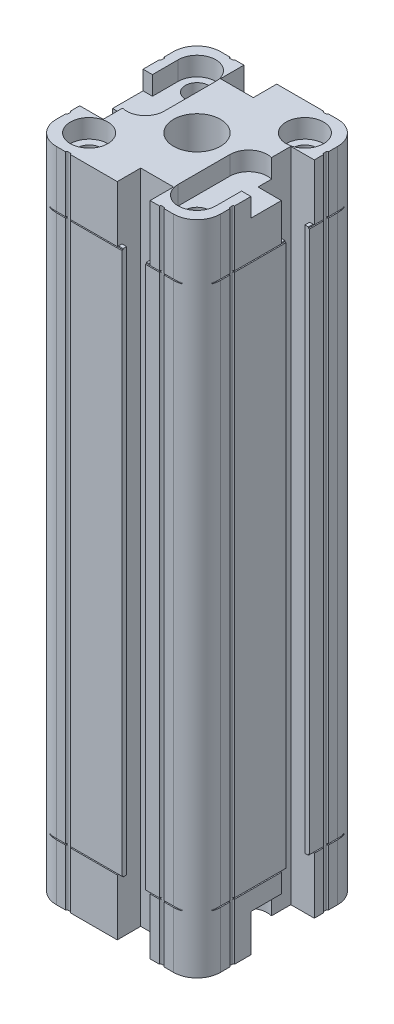
SolidWorks part; units mm, degrees
ref_plane "Front Plane" through (0, 0, 0) normal (0, 0, 1) x (1, 0, 0)
ref_plane "Top Plane" through (0, 0, 0) normal (0, 1, 0) x (1, 0, 0)
ref_plane "Right Plane" through (0, 0, 0) normal (1, 0, 0) x (0, 0, -1)
sketch "Sketch1" plane through (0, 0, 0) normal (0, 1, 0) x (1, 0, 0)
  line L1 (0, 0) -> (35, 0)
  line L2 (0, 0) -> (0, 35)
  line L3 (0, 35) -> (35, 35)
  line L4 (35, 0) -> (35, 35)
  dimension "D1" = 35
  dimension "D2" = 35
extrude "Boss-Extrude1" add sketch "Sketch1" along normal blind 140
sketch "Sketch2" plane through (0, 0, 0) normal (0, -1, 0) x (-1, 0, 0)
  line L0 (0, 0) -> (-35, 0) construction
  line L1 (0, 35) -> (0, 0) construction
  line L2 (-29, 6) -> (-29, 17) construction
  line L3 (-33, 6) -> (-33, 17)
  line L4 (-25, 6) -> (-25, 17)
  line L5 (-35, 0) -> (-35, 35) construction
  line L6 (-35, 35) -> (0, 35) construction
  line L7 (-6, 18) -> (-6, 29) construction
  line L8 (-10, 18) -> (-10, 29)
  line L9 (-2, 18) -> (-2, 29)
  circle A0 centre (-6, 6) radius 4
  circle A1 centre (-29, 29) radius 4
  arc A2 (-33, 6) -> (-25, 6) centre (-29, 6) ccw
  arc A3 (-25, 17) -> (-33, 17) centre (-29, 17) ccw
  arc A4 (-10, 18) -> (-2, 18) centre (-6, 18) ccw
  arc A5 (-2, 29) -> (-10, 29) centre (-6, 29) ccw
  point P10 (-29, 11.5)
  point P21 (-6, 23.5)
  dimension "D1" = 8
  dimension "D4" = 4
  dimension "D5" = 11
  dimension "D10" = 4
  dimension "D11" = 6
  dimension "D2" = 6
  dimension "D3" = 6
  dimension "D6" = 6
  dimension "D7" = 6
  dimension "D8" = 6
  dimension "D9" = 11
extrude "Cut-Extrude1" cut sketch "Sketch2" against normal blind 8
sketch "Sketch3" plane through (0, 0, 0) normal (0, -1, 0) x (-1, 0, 0)
  line L0 (0, 35) -> (0, 0) construction
  line L1 (-5, 23.5) -> (0, 23.5)
  line L2 (-5, 23.5) -> (-5, 14.127)
  line L3 (-5, 14.127) -> (0, 14.127)
  line L4 (0, 23.5) -> (0, 14.127)
  line L5 (-2, 18) -> (-2, 29) construction
  line L6 (-35, 20.873) -> (-30, 20.873)
  line L7 (-35, 20.873) -> (-35, 11.5)
  line L8 (-35, 11.5) -> (-30, 11.5)
  line L9 (-30, 20.873) -> (-30, 11.5)
  line L10 (-35, 0) -> (-35, 35) construction
  line L11 (-33, 17) -> (-33, 6) construction
  arc A2 (-25, 17) -> (-33, 17) centre (-29, 17) ccw construction
  arc A3 (-10, 18) -> (-2, 18) centre (-6, 18) ccw construction
  point P13 (-2, 23.5)
  point P25 (-32.5, 20.873)
  point P34 (-33, 11.5)
  dimension "D1" = 5
  dimension "D2" = 5
extrude "Cut-Extrude2" cut sketch "Sketch3" against normal up to surface (8 mm away) up to face at (6, 8, -23.5)
sketch "Sketch5" plane through (0, 0, 0) normal (0, -1, 0) x (1, 0, 0)
  line L0 (35, -20.873) -> (35, -35) construction
  line L1 (5, -17) -> (0, -17)
  line L2 (5, -17) -> (5, -10)
  line L3 (5, -10) -> (0, -10)
  line L4 (0, -17) -> (0, -10)
  line L5 (30, -18) -> (35, -18)
  line L6 (30, -18) -> (30, -25)
  line L7 (30, -25) -> (35, -25)
  line L8 (35, -18) -> (35, -25)
  line L9 (0, 0) -> (35, 0) construction
  line L10 (18, 0) -> (25, 0)
  line L11 (18, 0) -> (18, -5)
  line L12 (18, -5) -> (25, -5)
  line L13 (25, 0) -> (25, -5)
  line L14 (35, -35) -> (0, -35) construction
  line L15 (10, -35) -> (17, -35)
  line L16 (10, -35) -> (10, -30)
  line L17 (10, -30) -> (17, -30)
  line L18 (17, -35) -> (17, -30)
  circle A0 centre (6, -6) radius 4 construction
  circle A1 centre (29, -29) radius 4 construction
  dimension "D1" = 7
  dimension "D2" = 7
  dimension "D3" = 5
  dimension "D4" = 7
  dimension "D5" = 10
  dimension "D6" = 7
  dimension "D7" = 5
  dimension "D8" = 10
extrude "Cut-Extrude3" cut sketch "Sketch5" against normal blind 12
sketch "Sketch6" plane through (0, 12, 0) normal (0, -1, 0) x (1, 0, 0)
  line L6 (0, -16) -> (1, -16)
  line L7 (0, -10) -> (0, -17) construction
  line L8 (1, -16) -> (1, -17)
  line L9 (0, -17) -> (5, -17) construction
  line L10 (1, -17) -> (5, -17)
  line L11 (5, -17) -> (5, -10)
  line L12 (5, -10) -> (1, -10)
  line L13 (5, -10) -> (0, -10) construction
  line L14 (1, -10) -> (1, -11)
  line L15 (1, -11) -> (0, -11)
  line L16 (0, -11) -> (0, -16)
  line L17 (19, 0) -> (19, -1)
  line L18 (25, 0) -> (18, 0) construction
  line L19 (19, -1) -> (18, -1)
  line L20 (18, 0) -> (18, -5) construction
  line L21 (18, -1) -> (18, -5)
  line L22 (18, -5) -> (25, -5)
  line L23 (25, -5) -> (25, -1.01)
  line L24 (25, -5) -> (25, 0) construction
  line L25 (25, -1.01) -> (24, -1.01)
  line L26 (24, -1.01) -> (24, 0)
  line L27 (24, 0) -> (19, 0)
  line L28 (35, -19) -> (34, -19)
  line L29 (35, -25) -> (35, -18) construction
  line L30 (34, -19) -> (34, -18)
  line L31 (35, -18) -> (30, -18) construction
  line L32 (34, -18) -> (30, -18)
  line L33 (30, -18) -> (30, -25)
  line L34 (30, -25) -> (34, -25)
  line L35 (30, -25) -> (35, -25) construction
  line L36 (34, -25) -> (34, -24)
  line L37 (34, -24) -> (35, -24)
  line L38 (35, -24) -> (35, -19)
  line L39 (11, -35) -> (11, -34)
  line L40 (10, -35) -> (17, -35) construction
  line L41 (11, -34) -> (10, -34)
  line L42 (10, -30) -> (10, -35) construction
  line L43 (10, -34) -> (10, -30)
  line L44 (10, -30) -> (17, -30)
  line L45 (17, -30) -> (17, -34)
  line L46 (17, -35) -> (17, -30) construction
  line L47 (17, -34) -> (16, -34)
  line L48 (16, -34) -> (16, -35)
  line L49 (16, -35) -> (11, -35)
  dimension "D1" = 1
  dimension "D2" = 1
  dimension "D3" = 1
  dimension "D4" = 1
extrude "Cut-Extrude4" cut sketch "Sketch6" against normal blind 116
sketch "Sketch7" plane through (0, 140, 0) normal (0, 1, 0) x (1, 0, 0)
  line L0 (6, 29) -> (6, 18) construction
  line L1 (10, 29) -> (10, 18)
  line L2 (2, 29) -> (2, 18)
  line L3 (29, 17) -> (29, 6) construction
  line L4 (33, 17) -> (33, 6)
  line L5 (25, 17) -> (25, 6)
  arc A2 (10, 29) -> (2, 29) centre (6, 29) ccw
  arc A6 (2, 18) -> (10, 18) centre (6, 18) ccw
  circle A8 centre (29, 29) radius 4
  arc A9 (10, 29) -> (2, 29) centre (6, 29) ccw construction
  arc A10 (33, 17) -> (25, 17) centre (29, 17) ccw
  arc A11 (25, 6) -> (33, 6) centre (29, 6) ccw
  arc A12 (33, 17) -> (25, 17) centre (29, 17) ccw construction
  circle A13 centre (6, 6) radius 4
  point P4 (6, 23.5)
  point P14 (29, 11.5)
extrude "Cut-Extrude5" cut sketch "Sketch7" against normal blind 4
sketch "Sketch9" plane through (0, 140, 0) normal (0, 1, 0) x (1, 0, 0)
  line L1 (0, 23.5) -> (5, 23.5)
  line L2 (0, 23.5) -> (0, 14.127)
  line L3 (0, 14.127) -> (5, 14.127)
  line L4 (5, 23.5) -> (5, 14.127)
  line L5 (35, 20.873) -> (30, 20.873)
  line L6 (35, 20.873) -> (35, 11.5)
  line L7 (35, 11.5) -> (30, 11.5)
  line L8 (30, 20.873) -> (30, 11.5)
extrude "Cut-Extrude7" cut sketch "Sketch9" against normal up to surface (4 mm away) up to face at (6, 136, -23.5)
sketch "Sketch10" plane through (0, 140, 0) normal (0, 1, 0) x (1, 0, 0)
  line L1 (10, 30) -> (17, 30)
  line L2 (10, 30) -> (10, 35)
  line L3 (10, 35) -> (17, 35)
  line L4 (17, 30) -> (17, 35)
  line L5 (35, 25) -> (30, 25)
  line L6 (35, 25) -> (35, 18)
  line L7 (35, 18) -> (30, 18)
  line L8 (30, 25) -> (30, 18)
  line L9 (5, 10) -> (0, 10)
  line L10 (5, 10) -> (5, 17)
  line L11 (5, 17) -> (0, 17)
  line L12 (0, 10) -> (0, 17)
  line L13 (25, 5) -> (18, 5)
  line L14 (25, 5) -> (25, 0)
  line L15 (25, 0) -> (18, 0)
  line L16 (18, 5) -> (18, 0)
extrude "Cut-Extrude8" cut sketch "Sketch10" against normal blind 12
sketch "Sketch11" plane through (0, 140, 0) normal (0, 1, 0) x (1, 0, 0)
  line L0 (10, 35) -> (0, 35) construction
  line L1 (7, 35) -> (8, 35)
  line L2 (7, 35) -> (7, 34.75)
  line L3 (7, 34.75) -> (8, 34.75)
  line L4 (8, 35) -> (8, 34.75)
  line L5 (0, 35) -> (0, 23.5) construction
  line L6 (35, 35) -> (17, 35) construction
  line L7 (27, 35) -> (28, 35)
  line L8 (27, 35) -> (27, 34.75)
  line L9 (27, 34.75) -> (28, 34.75)
  line L10 (28, 35) -> (28, 34.75)
  line L11 (35, 25) -> (35, 35) construction
  line L12 (35, 0) -> (35, 11.5) construction
  line L13 (35, 28) -> (34.75, 28)
  line L14 (35, 28) -> (35, 27)
  line L15 (35, 27) -> (34.75, 27)
  line L16 (34.75, 28) -> (34.75, 27)
  line L17 (35, 8) -> (34.75, 8)
  line L18 (35, 8) -> (35, 7)
  line L19 (35, 7) -> (34.75, 7)
  line L20 (34.75, 8) -> (34.75, 7)
  line L21 (25, 0) -> (35, 0) construction
  line L22 (27, 0) -> (28, 0)
  line L23 (27, 0) -> (27, 0.25)
  line L24 (27, 0.25) -> (28, 0.25)
  line L25 (28, 0) -> (28, 0.25)
  line L26 (0, 0) -> (18, 0) construction
  line L27 (8, 0) -> (7, 0)
  line L28 (8, 0) -> (8, 0.25)
  line L29 (8, 0.25) -> (7, 0.25)
  line L30 (7, 0) -> (7, 0.25)
  line L31 (0, 10) -> (0, 0) construction
  line L32 (0, 8) -> (0.25, 8)
  line L33 (0, 8) -> (0, 7)
  line L34 (0, 7) -> (0.25, 7)
  line L35 (0.25, 8) -> (0.25, 7)
  line L36 (10, 35) -> (0, 35) construction
  line L37 (0, 28) -> (0.25, 28)
  line L38 (0, 28) -> (0, 27)
  line L39 (0, 27) -> (0.25, 27)
  line L40 (0.25, 28) -> (0.25, 27)
  dimension "D1" = 7
  dimension "D2" = 1
  dimension "D3" = 0.25
  dimension "D4" = 7
  dimension "D5" = 7
  dimension "D6" = 7
  dimension "D7" = 7
  dimension "D8" = 7
  dimension "D9" = 7
  dimension "D10" = 7
extrude "Cut-Extrude9" cut sketch "Sketch11" against normal through all
fillet "Fillet2" radius 0.25 16 edges at (0.25, 70, -7) (0.25, 70, -8) (7, 70, -0.25) (8, 70, -0.25) (28, 70, -0.25) (27, 70, -0.25) (34.75, 70, -8) (34.75, 70, -7) (34.75, 70, -27) (34.75, 70, -28) (27, 70, -34.75) (28, 70, -34.75) (7, 70, -34.75) (8, 70, -34.75) (0.25, 70, -27) (0.25, 70, -28)
sketch "Sketch12" plane through (0, 0, 0) normal (-1, 0, 0) x (0, 0, 1)
  line L0 (-35, 140) -> (-35, 0) construction
  line L1 (-35, 12.25) -> (-34.75, 12.25)
  line L2 (-35, 12.25) -> (-35, 12)
  line L3 (-35, 12) -> (-34.75, 12)
  line L4 (-34.75, 12.25) -> (-34.75, 12)
  line L5 (0, 140) -> (0, 0) construction
  line L6 (0, 12.25) -> (-0.25, 12.25)
  line L7 (0, 12.25) -> (0, 12)
  line L8 (0, 12) -> (-0.25, 12)
  line L9 (-0.25, 12.25) -> (-0.25, 12)
  line L10 (-35, 0) -> (-28, 0) construction
  line L11 (-7, 0) -> (0, 0) construction
  line L12 (-35, 140) -> (-28, 140) construction
  line L13 (-35, 128) -> (-34.75, 128)
  line L14 (-35, 128) -> (-35, 127.75)
  line L15 (-35, 127.75) -> (-34.75, 127.75)
  line L16 (-34.75, 128) -> (-34.75, 127.75)
  line L17 (0, 128) -> (-0.25, 128)
  line L18 (0, 128) -> (0, 127.75)
  line L19 (0, 127.75) -> (-0.25, 127.75)
  line L20 (-0.25, 128) -> (-0.25, 127.75)
  line L21 (-7, 140) -> (0, 140) construction
  dimension "D1" = 0.25
  dimension "D2" = 0.25
  dimension "D3" = 0.25
  dimension "D4" = 0.25
  dimension "D5" = 12
  dimension "D6" = 12
  dimension "D7" = 0.25
  dimension "D8" = 0.25
  dimension "D9" = 0.25
  dimension "D10" = 0.25
  dimension "D11" = 12
  dimension "D12" = 12
fillet "Fillet4" radius 5 4 edges at (35, 70, 0) (0, 70, 0) (35, 70, -35) (0, 70, -35)
extrude "Cut-Extrude12" cut sketch "Sketch12" against normal through all
sketch "Sketch14" plane through (0, 0, 0) normal (0, 0, 1) x (1, 0, 0)
  line L0 (35, 140) -> (35, 0) construction
  line L1 (0, 128) -> (0.25, 128)
  line L2 (0, 128) -> (0, 127.75)
  line L3 (0, 127.75) -> (0.25, 127.75)
  line L4 (0.25, 128) -> (0.25, 127.75)
  line L9 (0, 12.25) -> (0, 12) construction
  line L10 (0, 12.25) -> (0.25, 12.25)
  line L11 (0, 12.25) -> (0, 12)
  line L12 (0, 12) -> (0.25, 12)
  line L13 (0.25, 12.25) -> (0.25, 12)
  line L14 (0, 12.25) -> (0, 12) construction
  line L16 (35, 12.25) -> (34.75, 12.25)
  line L17 (35, 12.25) -> (35, 12)
  line L18 (35, 12) -> (34.75, 12)
  line L19 (34.75, 12.25) -> (34.75, 12)
  line L20 (35, 128) -> (34.75, 128)
  line L21 (35, 128) -> (35, 127.75)
  line L22 (35, 127.75) -> (34.75, 127.75)
  line L23 (34.75, 128) -> (34.75, 127.75)
  dimension "D1" = 0.25
  dimension "D2" = 0.25
  dimension "D3" = 0.25
  dimension "D5" = 0.25
  dimension "D6" = 0.25
  dimension "D7" = 0.25
  dimension "D8" = 0.25
extrude "Cut-Extrude13" cut sketch "Sketch14" against normal through all
sketch "Sketch15" plane through (0, 8, 0) normal (0, -1, 0) x (-1, 0, 0)
  circle A0 centre (-6, 6) radius 2.5
  circle A1 centre (-29, 29) radius 2.5
  circle A3 centre (-29, 6) radius 2.5
  circle A4 centre (-6, 29) radius 2.5
  dimension "D1" = 5
extrude "Cut-Extrude14" cut sketch "Sketch15" against normal up to vertex (4 mm away) up to point (0.25, 12, -3.4388)
thread "Thread2" pitch 0.8 method extrude profile "Thread Profile2" start angle 0, offset 0, length 0, pitch 0.8, diameter 5
ref_plane "Plane2" through (31.5, 8, -6) normal (0, 0, 1) x (1, 0, 0)
sketch "Thread Profile2" plane through (31.5, 8, -6) normal (0, 0, 1) x (1, 0, 0)
  line L0 (0, 0) -> (0, 0.8) construction
  line L11 (0, 0) -> (0, 0.7)
  line L12 (0, 0.7) -> (-0.433, 0.45)
  line L13 (-0.433, 0.45) -> (-0.433, 0.25)
  line L15 (-0.433, 0.25) -> (0, 0)
  line L17 (-0.433, 0.35) -> (0, 0.35) construction
  point P2 (0, 0)
  dimension "Pitch" = 0.8
  dimension "Profile_Angle" = 60
  dimension "Profile_Land" = 0.2
  dimension "Profile_Height" = 0.433
thread "Thread3" pitch 0.8 method extrude profile "Thread Profile3" start angle 0, offset 0, length 0, pitch 0.8, diameter 5
ref_plane "Plane3" through (8.5, 8, -29) normal (0, 0, 1) x (1, 0, 0)
sketch "Thread Profile3" plane through (8.5, 8, -29) normal (0, 0, 1) x (1, 0, 0)
  line L0 (0, 0) -> (0, 0.8) construction
  line L11 (0, 0) -> (0, 0.7)
  line L12 (0, 0.7) -> (-0.433, 0.45)
  line L13 (-0.433, 0.45) -> (-0.433, 0.25)
  line L15 (-0.433, 0.25) -> (0, 0)
  line L17 (-0.433, 0.35) -> (0, 0.35) construction
  point P2 (0, 0)
  dimension "Pitch" = 0.8
  dimension "Profile_Angle" = 60
  dimension "Profile_Land" = 0.2
  dimension "Profile_Height" = 0.433
sketch "Sketch24" plane through (0, 136, 0) normal (0, 1, 0) x (1, 0, 0)
  circle A0 centre (6, 29) radius 2.5
  circle A1 centre (29, 29) radius 2.5
  circle A2 centre (6, 6) radius 2.5
  circle A3 centre (29, 6) radius 2.5
  dimension "D1" = 5
extrude "Cut-Extrude15" cut sketch "Sketch24" against normal up to vertex (8 mm away) up to point (35, 128, -5)
sketch "Sketch33" plane through (0, 0, 0) normal (0, -1, 0) x (-1, 0, 0)
  circle A0 centre (-18, 18) radius 6
  dimension "D1" = 12
extrude "Cut-Extrude16" cut sketch "Sketch33" against normal blind 3
sketch "Sketch35" plane through (0, 140, 0) normal (0, 1, 0) x (1, 0, 0)
  line L0 (27, 35) -> (17, 35) construction
  line L1 (0, 17) -> (0, 23.5) construction
  circle A0 centre (17.5, 17.5) radius 5
  dimension "D1" = 10
  dimension "D2" = 17.5
  dimension "D3" = 17.5
extrude "Cut-Extrude19" cut sketch "Sketch15<3>" against normal through all contours A1 | A0
sketch "Sketch15<3>" plane through (0, 8, 0) normal (0, -1, 0) x (-1, 0, 0) same geometry as "Sketch15"
ref_plane "Plane4" through (0, 127.75, 0) normal (0, 1, 0) x (1, 0, 0)
sketch "Sketch36" plane through (0, 127.75, 0) normal (0, 1, 0) x (1, 0, 0)
  line L0 (0, 27) -> (0, 23.5) construction
  line L1 (8.5, 26.5) -> (26.5, 26.5)
  line L2 (8.5, 26.5) -> (8.5, 8.5)
  line L3 (8.5, 8.5) -> (26.5, 8.5)
  line L4 (26.5, 26.5) -> (26.5, 8.5)
  line L5 (8, 0) -> (18, 0) construction
  dimension "D1" = 18
  dimension "D2" = 18
  dimension "D3" = 8.5
  dimension "D4" = 8.5
extrude "Cut-Extrude20" cut sketch "Sketch36" against normal blind 110
extrude "Cut-Extrude21" cut sketch "Sketch35" against normal up to next
